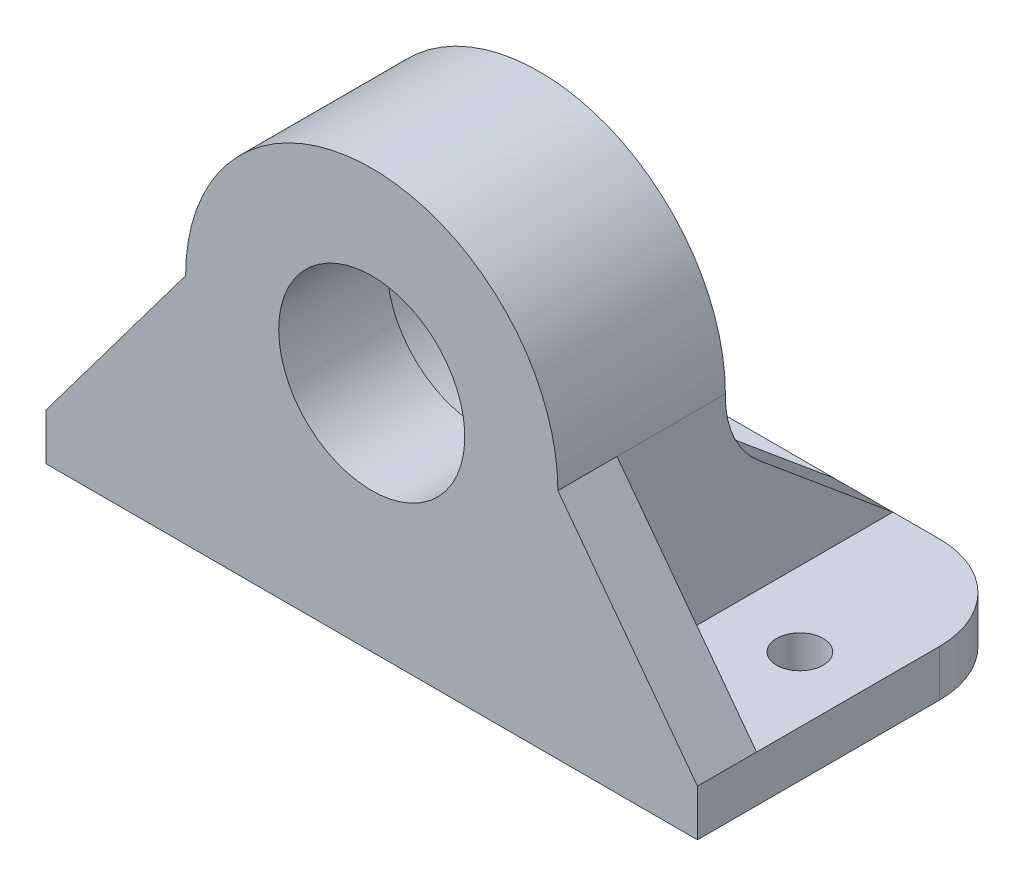
SolidWorks part; units mm, degrees
ref_plane "Front Plane" through (0, 0, 0) normal (0, 0, 1) x (1, 0, 0)
ref_plane "Top Plane" through (0, 0, 0) normal (0, 1, 0) x (1, 0, 0)
ref_plane "Right Plane" through (0, 0, 0) normal (1, 0, 0) x (0, 0, -1)
sketch "Sketch3" plane through (0, 0, 0) normal (0, 0, 1) x (1, 0, 0)
  line L0 (-20, 0) -> (-20, -20)
  line L1 (-20, -20) -> (20, -20)
  line L2 (20, -20) -> (20, 0)
  arc A0 (20, 0) -> (-20, 0) centre (0, 0) ccw
  dimension "D1" = 20
  dimension "D2" = 20
extrude "Boss-Extrude1" add sketch "Sketch3" along normal blind 18
sketch "Sketch6" plane through (0, -20, 0) normal (0, -1, 0) x (1, 0, 0)
  line L1 (-35, -18) -> (35, -18)
  line L2 (-35, -18) -> (-35, 18)
  line L3 (-35, 18) -> (35, 18)
  line L4 (35, -18) -> (35, 18)
  line L5 (-35, -18) -> (35, 18) construction
  line L6 (-35, 18) -> (35, -18) construction
  line L7 (-20, 18) -> (20, 18) construction
  line L10 (-28, 0) -> (-35, 0) construction
  line L11 (28, 0) -> (35, 0) construction
  line L12 (-20, 0) -> (20, 0) construction
  circle A0 centre (28, 0) radius 2.5
  circle A1 centre (-28, 0) radius 2.5
  point P6 (0, 0)
  dimension "D2" = 5
  dimension "D1" = 70
  dimension "D3" = 7
extrude "Boss-Extrude2" add sketch "Sketch6" along normal blind 5
sketch "Sketch7" plane through (0, 0, 0) normal (0, 0, -1) x (-1, 0, 0)
  circle A0 centre (0, 0) radius 10
  dimension "D1" = 20
extrude "Cut-Extrude1" cut sketch "Sketch7" against normal through all
sketch "Sketch8" plane through (0, 0, 0) normal (0, 0, -1) x (-1, 0, 0)
  circle A0 centre (0, 0) radius 14.2875
  dimension "D1" = 28.575
extrude "Cut-Extrude2" cut sketch "Sketch8" against normal blind 6.35
chamfer "Chamfer1" distance 0.5 angle 45 1 edges at (-14.2875, 0, 0)
sketch "Sketch9" plane through (20, 0, 0) normal (1, 0, 0) x (0, 0, -1)
  line L0 (18, -20) -> (0, -5)
  line L1 (0, -20) -> (0, 0) construction
  line L2 (0, -5) -> (0, -20)
  line L3 (0, -20) -> (18, -20)
  dimension "D1" = 15
extrude "Boss-Extrude3" add sketch "Sketch9" against normal blind 6.35
mirror "Mirror1" about plane through (0, 0, 0) normal (1, 0, 0) of "Boss-Extrude3"
sketch "Sketch10" plane through (0, 0, 18) normal (0, 0, 1) x (1, 0, 0)
  line L0 (-20, 0) -> (-35, -20)
  line L1 (-20, 0) -> (-20, -20) construction
  line L2 (-35, -20) -> (-20, -20)
  line L3 (-20, -20) -> (-20, 0)
  line L4 (20, 0) -> (20, -20)
  line L5 (20, -20) -> (20, 0) construction
  line L6 (20, -20) -> (35, -20)
  line L7 (35, -20) -> (20, 0)
  dimension "D1" = 20
extrude "Boss-Extrude4" add sketch "Sketch10" against normal blind 6.35
fillet "Fillet1" radius 10 2 edges at (-35, -22.5, -18) (35, -22.5, -18)
fillet "Fillet2" radius 10 2 edges at (-16.9583, -5, 0) (16.9583, -5, 0)
